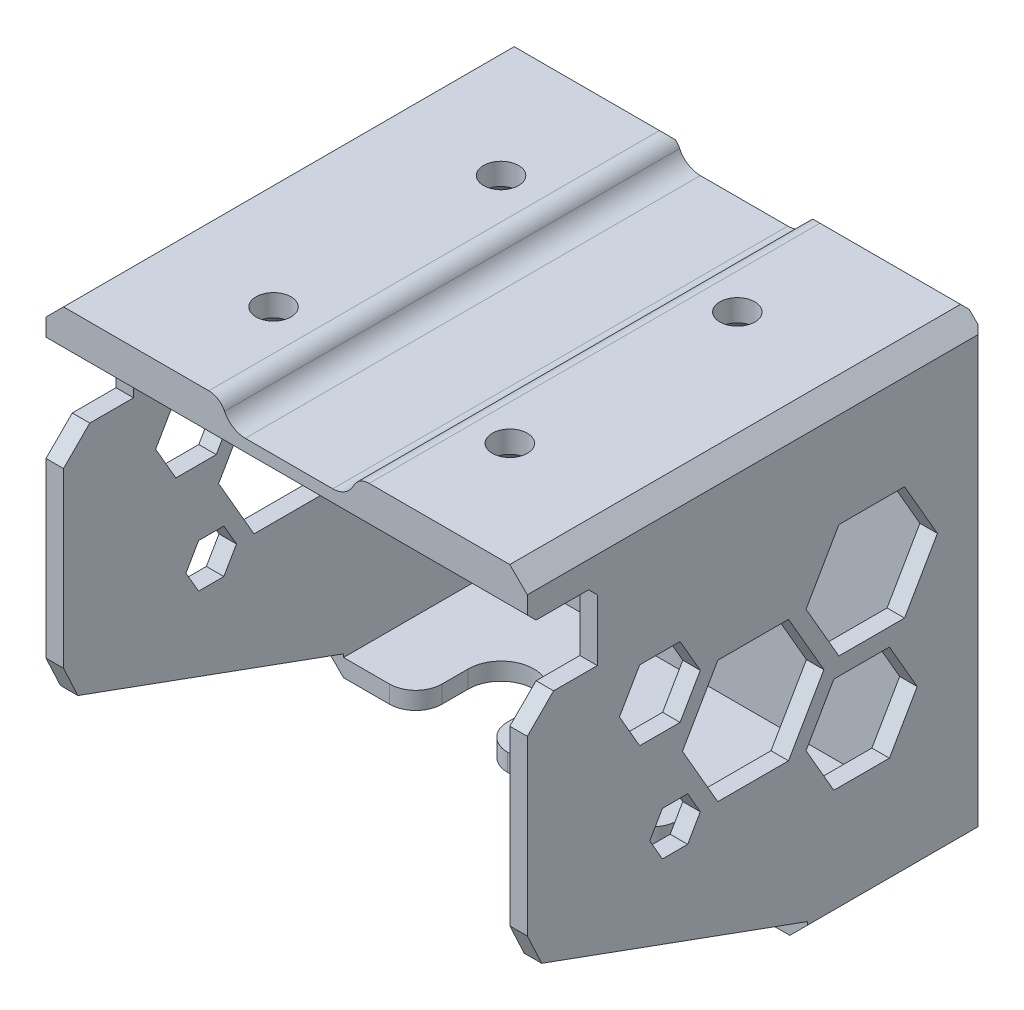
SolidWorks part; units mm, degrees
ref_plane "Plan de face" through (0, 0, 0) normal (0, 0, 1) x (1, 0, 0)
ref_plane "Plan de dessus" through (0, 0, 0) normal (0, 1, 0) x (1, 0, 0)
ref_plane "Plan de droite" through (0, 0, 0) normal (1, 0, 0) x (0, 0, -1)
sketch "Esquisse1" plane through (0, 0, 0) normal (0, 0, 1) x (1, 0, 0)
  line L0 (-25.5, 26.8578) -> (-25.5, -29.4808) construction
  line L1 (-25.5, -21.85) -> (25.5, -21.85)
  line L2 (-25.5, -21.85) -> (-25.5, 21.85)
  line L3 (-25.5, 21.85) -> (25.5, 21.85)
  line L4 (25.5, -21.85) -> (25.5, 21.85)
  line L5 (-25.5, -21.85) -> (25.5, 21.85) construction
  line L6 (-25.5, 21.85) -> (25.5, -21.85) construction
  line L8 (-25.5, 23.85) -> (-27.5, 23.85)
  line L9 (-25.5, 23.85) -> (-25.5, -23.85)
  line L10 (-25.5, -23.85) -> (-27.5, -23.85)
  line L11 (-27.5, 23.85) -> (-27.5, -23.85)
  line L12 (-25.5, 23.85) -> (25.5, 23.85)
  line L13 (-25.5, 23.85) -> (-25.5, 21.85)
  line L14 (-25.5, 21.85) -> (25.5, 21.85)
  line L15 (25.5, 23.85) -> (25.5, 21.85)
  line L16 (-25.5, -23.85) -> (25.5, -23.85)
  line L17 (-25.5, -23.85) -> (-25.5, -21.85)
  line L18 (-25.5, -21.85) -> (25.5, -21.85)
  line L19 (25.5, -23.85) -> (25.5, -21.85)
  line L20 (25.5, 23.85) -> (27.5, 23.85)
  line L21 (25.5, 23.85) -> (25.5, -23.85)
  line L22 (25.5, -23.85) -> (27.5, -23.85)
  line L23 (27.5, 23.85) -> (27.5, -23.85)
  point P0 (0, 0)
  dimension "D1" = 51
  dimension "D2" = 43.7
  dimension "D3" = 2
  dimension "D4" = 2
  dimension "D5" = 2
  dimension "D6" = 2
extrude "Boss.-Extru.1" add sketch "Esquisse1" along normal blind 50 contours L15 L12 L9 L3 | L8 L11 L10 L9 L2 | L23 L20 L15 L4 L19 L22
sketch "Esquisse2" plane through (0, 0, 0) normal (0, 0, -1) x (-1, 0, 0)
  line L1 (27.5, -23.85) -> (-27.5, -23.85)
  line L2 (27.5, -23.85) -> (27.5, 23.85)
  line L3 (27.5, 23.85) -> (-27.5, 23.85)
  line L4 (-27.5, -23.85) -> (-27.5, 23.85)
extrude "Boss.-Extru.2" add sketch "Esquisse2" along normal blind 2
sketch "Esquisse3" plane through (0, -23.85, 0) normal (0, -1, 0) x (1, 0, 0)
  line L0 (27.5, 50) -> (27.5, -2) construction
  line L1 (-27.5, -2) -> (27.5, -2)
  line L2 (-27.5, -2) -> (-27.5, 18)
  line L3 (-27.5, 18) -> (27.5, 18)
  line L4 (27.5, -2) -> (27.5, 18)
  dimension "D1" = 20
extrude "Boss.-Extru.3" add sketch "Esquisse3" along normal blind 2
sketch "Esquisse4" plane through (0, 23.85, 0) normal (0, 1, 0) x (1, 0, 0)
  line L1 (27.5, -50) -> (-27.5, -50)
  line L2 (27.5, -50) -> (27.5, 2)
  line L3 (27.5, 2) -> (-27.5, 2)
  line L4 (-27.5, -50) -> (-27.5, 2)
extrude "Boss.-Extru.4" add sketch "Esquisse4" along normal blind 3
sketch "Esquisse6" plane through (0, 21.85, 0) normal (0, -1, 0) x (1, 0, 0)
  line L1 (-25.5, 50) -> (-25.5, 0) construction
  line L2 (-25.5, 50) -> (25.5, 50) construction
  line L3 (25.5, 50) -> (25.5, 0) construction
  line L4 (-25.5, 25) -> (25.5, 25) construction
  line L6 (0, 50) -> (0, 0) construction
  line L7 (-25.5, 38) -> (25.5, 38) construction
  circle A0 centre (-13.5, 38) radius 2
  circle A1 centre (13.5, 38) radius 2
  circle A2 centre (-13.5, 12) radius 2
  circle A3 centre (13.5, 12) radius 2
  point P0 (13.5, 12)
  point P1 (13.5, 38)
  point P8 (-13.5, 12)
  point P18 (-13.5, 38)
  dimension "D3" = 4
  dimension "D1" = 12
  dimension "D2" = 12
extrude "Enlèv. mat.-Extru.1" cut sketch "Esquisse6" against normal up to surface (5 mm away) up to face at (0, 26.85, 24)
chamfer "Chanfrein2" distance 33 angle 20 2 edges at (-26.5, -23.85, 50) (26.5, -23.85, 50)
chamfer "Chanfrein4" distance 2 angle 45 2 edges at (27.5, -25.85, 8) (-27.5, -25.85, 8)
chamfer "Chanfrein5" distance 2 angle 45 2 edges at (27.5, 26.85, 24) (-27.5, 26.85, 24)
chamfer "Chanfrein8" distance 0.5 angle 45 4 edges at (0, -25.85, -2) (-27.5, 0.5, -2) (0, 26.85, -2) (27.5, 0.5, -2)
sketch "Esquisse7" plane through (-27.5, 0, 0) normal (-1, 0, 0) x (0, 0, 1)
  line L0 (46.1715, 9.8923) -> (46.1715, -9.6456) construction
  text T0 "<b>          Serrure</b>\r\n<b>       connectée</b>" font "Century Gothic" height in points 8
extrude "Enlèv. mat.-Extru.2" cut sketch "Esquisse7" against normal blind 0.5
sketch "Esquisse9" plane through (0, 0, -2) normal (0, 0, -1) x (-1, 0, 0)
  line L0 (27, 0.5) -> (-27, 0.5) construction
  line L1 (27, -24.35) -> (27, 25.35) construction
  line L2 (-27, 25.35) -> (-27, -24.35) construction
  text T0 "<b>      Leeroy Jenkins !!</b>"
extrude "Enlèv. mat.-Extru.3" cut sketch "Esquisse9" against normal blind 0.5
sketch "Esquisse13" plane through (27.5, 0, 0) normal (1, 0, 0) x (0, 0, -1)
  line L0 (-50, 24.85) -> (-50, -11.839) construction
  line L1 (-50, 21.85) -> (-42, 21.85)
  line L2 (-50, 21.85) -> (-50, 13.85)
  line L3 (-50, 13.85) -> (-42, 13.85)
  line L4 (-42, 21.85) -> (-42, 13.85)
  line L5 (1.5, 24.85) -> (-50, 24.85) construction
  dimension "D1" = 3
  dimension "D2" = 8
  dimension "D3" = 8
extrude "Enlèv. mat.-Extru.7" cut sketch "Esquisse13" against normal up to surface (55 mm away) up to face at (-27.5, 3.1305, 42.2584)
chamfer "Chanfrein10" distance 3 angle 45 1 edges at (26.5, 13.85, 50)
chamfer "Chanfrein11" distance 1 angle 45 2 edges at (26.5, 21.85, 42) (-26.5, 21.85, 42)
chamfer "Chanfrein12" distance 1 angle 45 1 edges at (0, 21.85, 50)
chamfer "Chanfrein13" distance 1.75 distance2 2.5 4 edges at (-13.5, 21.85, 36) (13.5, 21.85, 10) (-13.5, 21.85, 14) (13.5, 21.85, 40)
sketch "Esquisse14" plane through (0, 0, 50) normal (0, 0, 1) x (1, 0, 0)
  line L0 (-4.7316, 26.85) -> (5.2684, 26.85) construction
  line L1 (-25.5, 26.85) -> (25.5, 26.85) construction
  line L2 (-4.7316, 29.4711) -> (5.2684, 29.4711)
  line L3 (-4.7316, 24.2289) -> (5.2684, 24.2289)
  arc A0 (-4.7316, 29.4711) -> (-4.7316, 24.2289) centre (-4.7316, 26.85) ccw
  arc A1 (5.2684, 24.2289) -> (5.2684, 29.4711) centre (5.2684, 26.85) ccw
  point P4 (0.2684, 26.85)
  dimension "D1" = 5
extrude "Enlèv. mat.-Extru.8" cut sketch "Esquisse14" against normal up to next
fillet "Congé1" radius 2 2 edges at (-7.3527, 26.85, 24.25) (7.8896, 26.85, 24.25)
sketch "Esquisse15" plane through (27.5, 0, 0) normal (1, 0, 0) x (0, 0, -1)
  line L0 (1.5, 0.5) -> (-49.8827, 0.5) construction
  line L1 (-32.2742, 0.5) -> (-28.2328, -6.5)
  line L2 (-28.2328, -6.5) -> (-20.1499, -6.5)
  line L3 (-20.1499, -6.5) -> (-16.1084, 0.5)
  line L4 (-16.1084, 0.5) -> (-20.1499, 7.5)
  line L5 (-20.1499, 7.5) -> (-28.2328, 7.5)
  line L6 (-28.2328, 7.5) -> (-32.2742, 0.5)
  line L7 (1.5, -23.85) -> (1.5, 24.85) construction
  line L8 (-20.1499, -6.5) -> (9.8753, -6.5) construction
  line L9 (-20.1499, 7.5) -> (2.1435, 7.5) construction
  line L10 (-18.1499, -6.5002) -> (-14.9743, -12.0001)
  line L11 (-14.9743, -12.0001) -> (-8.6234, -11.9999)
  line L12 (-8.6234, -11.9999) -> (-5.4482, -6.4998)
  line L13 (-5.4482, -6.4998) -> (-8.6238, -0.9999)
  line L14 (-8.6238, -0.9999) -> (-14.9746, -1.0001)
  line L15 (-14.9746, -1.0001) -> (-18.1499, -6.5002)
  line L16 (-28.2328, -6.5) -> (-42.4905, -6.5) construction
  line L17 (-3.1388, 7.5) -> (-6.8916, 14)
  line L18 (-6.8916, 14) -> (-14.3971, 14)
  line L19 (-14.3971, 14) -> (-18.1499, 7.5)
  line L20 (-18.1499, 7.5) -> (-14.3971, 1)
  line L21 (-14.3971, 1) -> (-6.8916, 1)
  line L22 (-6.8916, 1) -> (-3.1388, 7.5)
  line L23 (-28.2328, 7.5) -> (-42.4905, 7.5) construction
  line L24 (-28.2328, 7.5) -> (-28.2328, 27.6475) construction
  line L26 (-30.2328, 7.5) -> (-32.5422, 11.5)
  line L27 (-32.5422, 11.5) -> (-37.161, 11.5)
  line L28 (-37.161, 11.5) -> (-39.4704, 7.5)
  line L29 (-39.4704, 7.5) -> (-37.161, 3.5)
  line L30 (-37.161, 3.5) -> (-32.5422, 3.5)
  line L31 (-32.5422, 3.5) -> (-30.2328, 7.5)
  line L32 (-30.2328, -6.5) -> (-31.6762, -4)
  line L33 (-31.6762, -4) -> (-34.5629, -4)
  line L34 (-34.5629, -4) -> (-36.0063, -6.5)
  line L35 (-36.0063, -6.5) -> (-34.5629, -9)
  line L36 (-34.5629, -9) -> (-31.6762, -9)
  line L37 (-31.6762, -9) -> (-30.2328, -6.5)
  circle A0 centre (-24.1913, 0.5) radius 7 construction
  circle A1 centre (-11.799, -6.5) radius 5.5 construction
  circle A2 centre (-10.6443, 7.5) radius 6.5 construction
  circle A3 centre (-34.8516, 7.5) radius 4 construction
  circle A4 centre (-33.1195, -6.5) radius 2.5 construction
  dimension "D1" = 14
  dimension "D4" = 11
  dimension "D5" = 13
  dimension "D7" = 8
  dimension "D8" = 5
  dimension "D2" = 2
  dimension "D3" = 2
  dimension "D6" = 2
  dimension "D9" = 2
extrude "Enlèv. mat.-Extru.10" cut sketch "Esquisse15" against normal up to surface (55 mm away) up to face at (-27.5, 3.1305, 42.2584)
sketch "Esquisse16" plane through (0, -25.85, 0) normal (0, -1, 0) x (1, 0, 0)
  line L0 (-17.25, 12) -> (-17.25, 18)
  line L1 (25.5, 18) -> (-25.5, 18) construction
  line L2 (-17.25, 18) -> (-9.75, 18)
  line L3 (-9.75, 18) -> (-9.75, 12)
  line L4 (-17.25, 12) -> (-9.75, 12)
  line L5 (9.75, 12) -> (17.25, 12)
  line L6 (17.25, 12) -> (17.25, 18)
  line L7 (17.25, 18) -> (9.75, 18)
  line L8 (9.75, 18) -> (9.75, 12)
  circle A0 centre (-13.5, 12) radius 3.75
  circle A1 centre (13.5, 12) radius 3.75
  line M5 (25.5, 18) -> (-25.5, 18)
extrude "Enlèv. mat.-Extru.11" cut sketch "Esquisse16" against normal up to surface (2 mm away) contours A0 L3 L0 M5 | L4 A0 | L4 A0 | L5 A1 | L5 A1 | A1 L6 L8 M5 up to face at (0, -23.85, 9)
fillet "Congé2" radius 3 4 edges at (17.25, -24.85, 18) (9.75, -24.85, 18) (-9.75, -24.85, 18) (-17.25, -24.85, 18)
chamfer "Chanfrein14" distance 1.75 angle 45 2 edges at (26.5, -11.839, 50) (-26.5, -11.839, 50)
